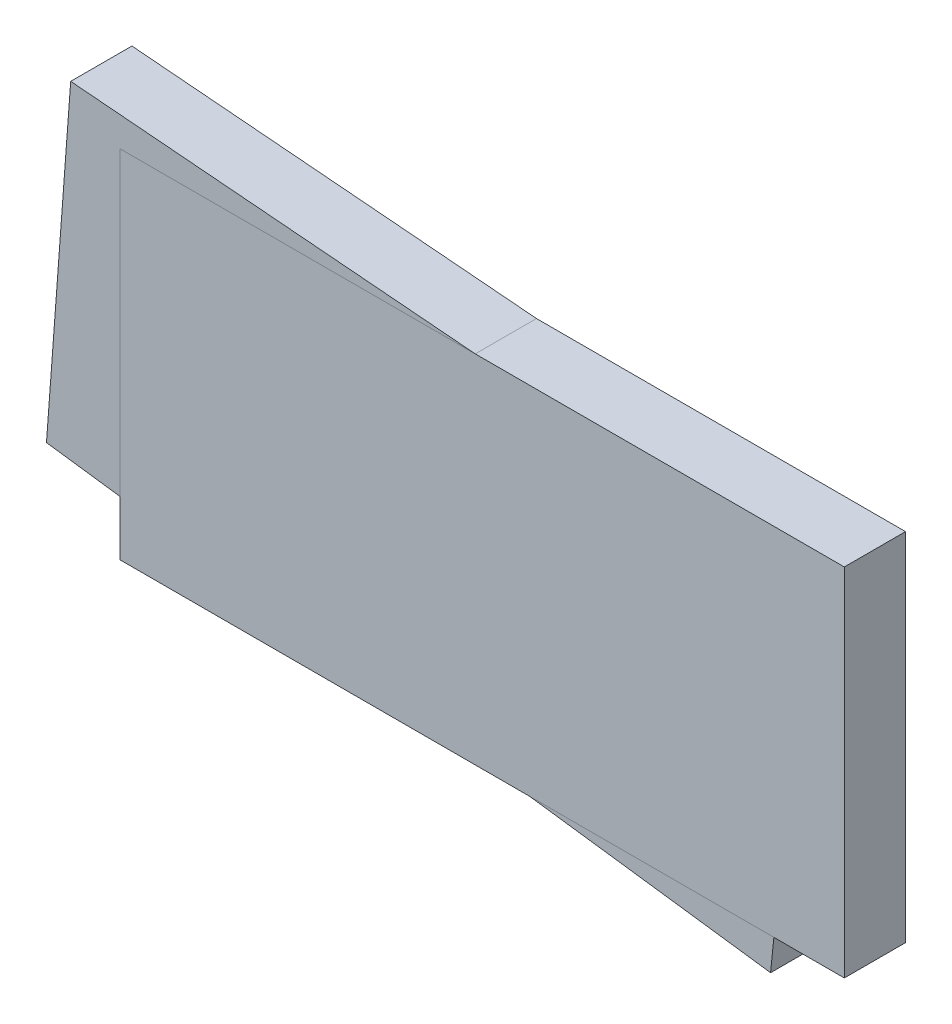
SolidWorks part; units mm, degrees
ref_plane "Ebene vorne" through (0, 0, 0) normal (0, 0, 1) x (1, 0, 0)
ref_plane "Ebene oben" through (0, 0, 0) normal (0, 1, 0) x (1, 0, 0)
ref_plane "Ebene rechts" through (0, 0, 0) normal (1, 0, 0) x (0, 0, -1)
sketch "Skizze1" plane through (0, 0, 0) normal (0, 0, 1) x (1, 0, 0)
  line L1 (-88.7322, -43.6075) -> (88.7322, -43.6075)
  line L2 (-88.7322, -43.6075) -> (-88.7322, 43.6075)
  line L3 (-88.7322, 43.6075) -> (88.7322, 43.6075)
  line L4 (88.7322, -43.6075) -> (88.7322, 43.6075)
  line L5 (-88.7322, -43.6075) -> (88.7322, 43.6075) construction
  line L6 (-88.7322, 43.6075) -> (88.7322, -43.6075) construction
  point P0 (0, 0)
extrude "Aufsatz-Linear austragen1" add sketch "Skizze1" along normal blind 15
ref_plane "PL1_1" through (0, 0, 0) normal (1, 0, 0) x (0, 0, -1)
ref_plane "PL2_1" through (0, -43.6075, 0) normal (0, -1, 0) x (-1, 0, 0)
ref_plane "PL3_1" through (0, 0, 15) normal (0, 0, 1) x (1, 0, 0)
ref_axis "A1" through (-44.3927, -43.6075, 15) along (1, 0, 0)
ref_point "P1"
sketch "Skizze2" plane through (0, 0, 0) normal (0, 0, 1) x (1, 0, 0)
  line L0 (70.6683, -51.5239) -> (79.6139, 36.8272)
  line L1 (79.6139, 36.8272) -> (-100.8005, 51.8734)
  line L2 (-100.8005, 51.8734) -> (-106.7377, -27.7478)
  line L3 (-106.7377, -27.7478) -> (70.6683, -51.5239)
  point P3 (-111.297, 52.2613)
  point P5 (98.9686, 67.7398)
  point P6 (102.7109, 54.5996)
  point P7 (-85.8386, 40.8011)
  point P8 (-109.2281, -61.3118)
  point P9 (-82.015, -30.8066)
  point P10 (-101.949, 67.8235)
  point P11 (-82.1135, -36.5917)
  point P12 (-100.8005, 51.8734)
  point P13 (79.6139, 36.8272)
  point P14 (87.3755, -52.9458)
  point P15 (-106.7377, -27.7478)
  point P16 (70.6683, -51.5239)
extrude "Aufsatz-Linear austragen2" add sketch "Skizze2" along normal blind 15 separate body
ref_plane "PL1" through (0, 0, 15) normal (0, 0, 1) x (1, 0, 0)
ref_plane "PL2" through (-5.5365, -41.3109, 0) normal (-0.1328, -0.9911, 0) x (-0.9911, 0.1328, 0)
ref_axis "Achse2" through (-74.2697, -32.0992, 15) along (0.9911, -0.1328, 0)
ref_point "Punkt2"
ref_point "Punkt3"
ref_point "Punkt4"
ref_point "Punkt5"
ref_axis "Achse3" through (-106.7377, -27.7478, 15) along (0.9877, -0.1324, -0.0835)
ref_axis "Achse4" through (-106.7377, -27.7478, 0) along (0.9877, -0.1324, 0.0835)
ref_point "Punkt6"
ref_axis "A2" through (70.6683, -51.5239, 15) along (-0.9911, 0.1328, 0)
ref_plane "PL3" through (-18.0347, -39.6358, 7.5) normal (-0.9911, 0.1328, 0) x (0, 0, 1)
ref_point "P2"
